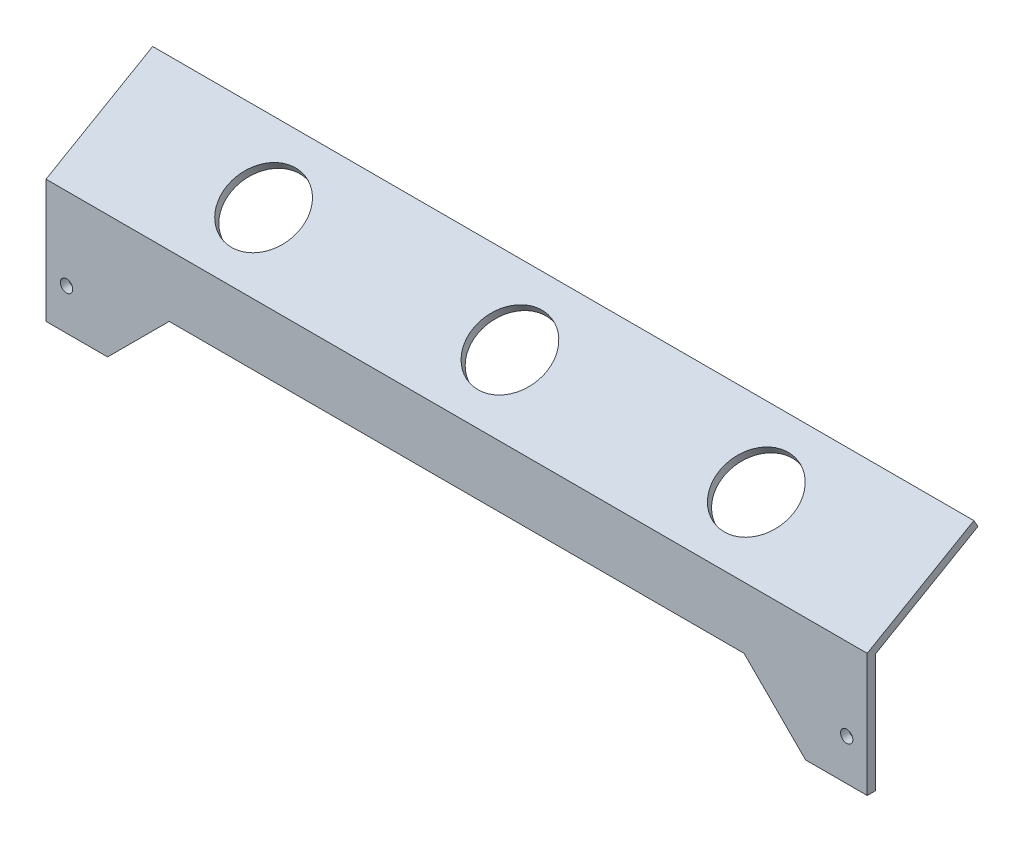
SolidWorks part; units mm, degrees
material "Perspex (TM) GS Acrylic Cast Sheet"
ref_plane "Front Plane" through (0, 0, 0) normal (0, 0, 1) x (1, 0, 0)
ref_plane "Top Plane" through (0, 0, 0) normal (0, 1, 0) x (1, 0, 0)
ref_plane "Right Plane" through (0, 0, 0) normal (1, 0, 0) x (0, 0, -1)
sketch "Sketch1" plane through (0, 0, 0) normal (1, 0, 0) x (0, 0, -1)
  line L0 (0, 0) -> (2, 0)
  line L1 (55, 0) -> (-55, 0) construction
  line L2 (2, 0) -> (2, 28.8453)
  line L3 (2, 28.8453) -> (26.9808, 43.2679)
  line L4 (26.9808, 43.2679) -> (25.9808, 45)
  line L5 (25.9808, 45) -> (0, 30)
  line L6 (0, 55) -> (0, -55) construction
  line L7 (0, 30) -> (0, 0)
  dimension "D1" = 2
  dimension "D2" = 2
  dimension "D3" = 30
  dimension "D4" = 120
  dimension "D5" = 30
extrude "Boss-Extrude1" add sketch "Sketch1" along normal mid plane 200
sketch "Sketch2" plane through (0, 0, 0) normal (0, 0, 1) x (1, 0, 0)
  line L0 (14.8394, 0) -> (-14.8394, 0) construction
  line L1 (-100, 30) -> (-100, 0) construction
  line L2 (100, 30) -> (100, 0) construction
  line L3 (-85, 0) -> (-70, 15)
  line L4 (100, 0) -> (-100, 0) construction
  line L5 (-70, 15) -> (70, 15)
  line L6 (70, 15) -> (85, 0)
  line L7 (85, 0) -> (-85, 0)
  line L8 (0, -14.8394) -> (0, 14.8394) construction
  circle A0 centre (-95, 10) radius 1.5
  circle A1 centre (95, 10) radius 1.5
  dimension "D1" = 3
  dimension "D2" = 10
  dimension "D3" = 5
  dimension "D4" = 5
  dimension "D5" = 85
  dimension "D6" = 85
  dimension "D7" = 15
  dimension "D8" = 45
extrude "Cut-Extrude1" cut sketch "Sketch2" against normal blind 10
sketch "Sketch4" plane through (0, 22.5, 12.9904) normal (0, 0.866, 0.5) x (1, 0, 0)
  line L0 (0, -14.8394) -> (0, 14.8394) construction
  line L1 (100, 45) -> (-100, 45) construction
  circle A0 centre (0, 30) radius 9
  circle A1 centre (60, 30) radius 9
  circle A2 centre (-60, 30) radius 9
  dimension "D1" = 18
  dimension "D2" = 60
  dimension "D3" = 60
  dimension "D4" = 15
extrude "Cut-Extrude2" cut sketch "Sketch4" against normal blind 10
